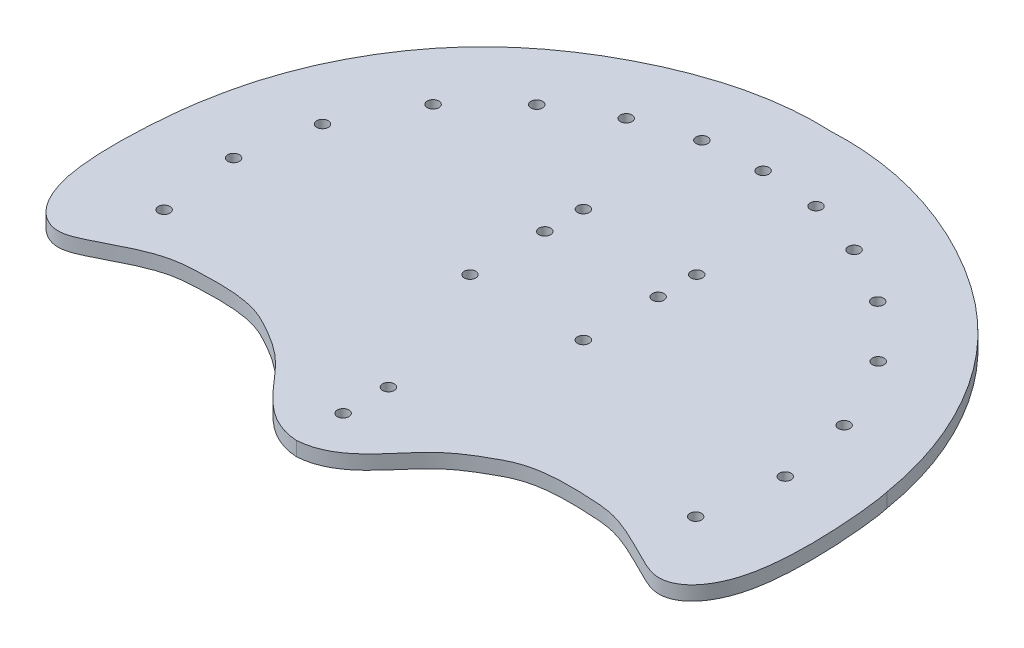
SolidWorks part; units mm, degrees
material "6061-T6 (SS)"
ref_plane "Front Plane" through (0, 0, 0) normal (0, 0, 1) x (1, 0, 0)
ref_plane "Top Plane" through (0, 0, 0) normal (0, 1, 0) x (1, 0, 0)
ref_plane "Right Plane" through (0, 0, 0) normal (1, 0, 0) x (0, 0, -1)
sketch "Sketch3" plane through (0, 0, 0) normal (0, 1, 0) x (1, 0, 0)
  line L0 (0, 0) -> (0, 159.1899) construction
  line L1 (0, 0) -> (0, -140.5301) construction
  line L2 (0, 0) -> (-190.5, 0) construction
  line L3 (0, 0) -> (190.5, 0) construction
  spline S0 degree 3 poles (-190.5, 0) (-184.3927, 37.537) (-157.2613, 93.9641) (-82.3875, 146.6227) (-31.3114, 160.7999) (0, 159.1899) knots 0 0 0 0 0.424401 0.65637 1 1 1 1
  spline S1 degree 3 poles (-190.5, 0) (-192.064, -4.9635) (-201.9672, -83.3146) (-174.6966, -109.29) (-151.6301, -100.568) (-131.4108, -87.7198) (-96.8436, -85.3754) (-78.6925, -86.2588) (-58.8335, -96.8794) (-37.3059, -109.9358) (-21.3496, -139.1148) (0, -140.5301) knots 0 0 0 0 0.166997 0.292321 0.319633 0.426735 0.458914 0.609242 0.64191 0.766802 1 1 1 1
  spline S2 degree 3 poles (190.5, 0) (192.064, -4.9635) (201.9672, -83.3146) (174.6966, -109.29) (151.6301, -100.568) (131.4108, -87.7198) (96.8436, -85.3754) (78.6925, -86.2588) (58.8335, -96.8794) (37.3059, -109.9358) (21.3496, -139.1148) (0, -140.5301) knots 0 0 0 0 0.166997 0.292321 0.319633 0.426735 0.458914 0.609242 0.64191 0.766802 1 1 1 1
  spline S3 degree 3 poles (190.5, 0) (184.3927, 37.537) (157.2613, 93.9641) (82.3875, 146.6227) (31.3114, 160.7999) (0, 159.1899) knots 0 0 0 0 0.424401 0.65637 1 1 1 1
  dimension "D1" = 381
  dimension "D2" = 299.72
  dimension "D3" = 159.1899
  dimension "D4" = 86.8953
  dimension "D5" = 104.4979
  dimension "D6" = 29.1616
  dimension "D7" = 92.2742
  dimension "D8" = 108.411
  dimension "D9" = 67.4883
  dimension "D10" = 43.7314
  dimension "D11" = 117.6915
  dimension "D12" = 162.2568
  dimension "D13" = 89.4522
  dimension "D14" = 140.1036
  dimension "D15" = 175.0666
  dimension "D16" = 50.2669
  dimension "D17" = 101.3666
  dimension "D18" = 138.1225
  dimension "D19" = 155.1557
  dimension "D20" = 192.0074
  dimension "D21" = 193.9268
  dimension "D23" = 76.6666
extrude "Boss-Extrude1" add sketch "Sketch3" along normal blind 7.9502 from surface starting at plane "Top Plane"
sketch "Sketch5" plane through (0, 0, 0) normal (0, -1, 0) x (1, 0, 0)
  line L0 (0, 0) -> (0, -20.32) construction
  line L1 (31.75, -52.07) -> (-31.75, -52.07)
  line L2 (31.75, -52.07) -> (31.75, 11.43)
  line L3 (31.75, 11.43) -> (-31.75, 11.43)
  line L4 (-31.75, -52.07) -> (-31.75, 11.43)
  line L5 (31.75, -52.07) -> (-31.75, 11.43) construction
  line L6 (31.75, 11.43) -> (-31.75, -52.07) construction
  line L7 (-31.75, -52.07) -> (-31.75, -30.48)
  line L8 (-31.75, -30.48) -> (31.75, -30.48) construction
  line L9 (0, -20.32) -> (140.7253, -20.32) construction
  line L10 (0, -20.32) -> (0, -97.1287) construction
  line L11 (0, -20.32) -> (31.9753, -118.7297) construction
  line L13 (0, -20.32) -> (63.8443, -108.1942) construction
  line L14 (0, -20.32) -> (95.5392, -89.7333) construction
  line L15 (124.7166, -60.8429) -> (0, -20.32) construction
  line L16 (0, -20.32) -> (154.5508, 21.0918) construction
  line L17 (0, -20.32) -> (148.922, 65.6601) construction
  line L18 (0, -20.32) -> (-31.9753, -118.7297) construction
  line L19 (0, -20.32) -> (-63.8443, -108.1942) construction
  line L20 (0, -20.32) -> (-95.5392, -89.7333) construction
  line L21 (-124.7166, -60.8429) -> (0, -20.32) construction
  line L22 (0, -20.32) -> (-154.5508, 21.0918) construction
  line L23 (0, -20.32) -> (-148.922, 65.6601) construction
  spline S0 degree 3 poles (-148.922, 65.6601) (-157.8584, 40.2253) (-156.2837, 8.5854) (-143.1202, -28.9506) (-139.3242, -37.3463) (-130.3709, -53.1962) (-125.215, -60.649) (-118.0488, -69.1403) (-116.5795, -70.7975) (-113.5719, -74.0252) (-112.0368, -75.592) (-107.2801, -80.2116) (-103.9215, -83.1695) (-93.3361, -91.6595) (-85.5959, -96.8074) (-76.3408, -101.9556) (-75.3049, -102.5187) (-73.219, -103.6268) (-72.1677, -104.1726) (-69.0049, -105.7765) (-66.8862, -106.8006) (-60.5068, -109.7299) (-56.2231, -111.4921) (-47.6308, -114.6027) (-43.3223, -115.9511) (-34.7104, -118.209) (-30.4072, -119.1185) (-21.8242, -120.4791) (-17.5446, -120.9304) (-11.1443, -121.2499) (-9.0138, -121.2968) (-5.8216, -121.2757) (-4.1848, -121.2414) (-2.5489, -121.1705) (-1.9677, -121.1408) (-1.9605, -121.1404) (-1.2995, -121.1064) (-0.6497, -121.073) (0, -121.0396) knots -0.292878 -0.292878 -0.292878 -0.292878 0.125 0.125 0.25 0.25 0.375 0.375 0.40625 0.40625 0.4375 0.4375 0.5 0.5 0.625 0.625 0.640625 0.640625 0.65625 0.65625 0.6875 0.6875 0.75 0.75 0.8125 0.8125 0.875 0.875 0.9375 0.9375 0.96875 0.96875 0.984375 0.992798 0.992798 0.99292 0.99292 1 1 1 1
  spline S5 degree 3 poles (998.6789, -69.6893) (665.1581, -86.8384) (331.6156, -103.9885) (-1.9268, -121.1387) (-1.9605, -121.1404) (-1.9677, -121.1408) (-2.5489, -121.1705) (-4.1848, -121.2414) (-5.8216, -121.2757) (-9.0138, -121.2968) (-11.1443, -121.2499) (-17.5446, -120.9304) (-21.8242, -120.4791) (-30.4072, -119.1185) (-34.7104, -118.209) (-43.3223, -115.9511) (-47.6308, -114.6027) (-56.2231, -111.4921) (-60.5068, -109.7299) (-66.8862, -106.8006) (-69.0049, -105.7765) (-72.1677, -104.1726) (-73.219, -103.6268) (-75.3049, -102.5187) (-76.3408, -101.9556) (-85.5959, -96.8074) (-93.3361, -91.6595) (-103.9215, -83.1695) (-107.2801, -80.2116) (-112.0368, -75.592) (-113.5719, -74.0252) (-116.5795, -70.7975) (-118.0488, -69.1403) (-125.215, -60.649) (-130.3709, -53.1962) (-139.3242, -37.3463) (-143.1202, -28.9506) (-198.5095, 128.9933) (-22.362, 351.6373) (651.8169, -587.5188) knots -3.627409 -3.627409 -3.627409 -3.627409 0.006836 0.00708 0.00708 0.007202 0.007202 0.015625 0.03125 0.03125 0.0625 0.0625 0.125 0.125 0.1875 0.1875 0.25 0.25 0.3125 0.3125 0.34375 0.34375 0.359375 0.359375 0.375 0.375 0.5 0.5 0.5625 0.5625 0.59375 0.59375 0.625 0.625 0.75 0.75 0.875 0.875 3.034324 3.034324 3.034324 3.034324 only from (0, -121.0396) to (-152.8945, 6.1184)
  spline S6 degree 3 poles (-1687.8289, -2297.0686) (-150.4269, 537.0593) (218.9922, 187.4002) (143.1202, -28.9506) (139.3242, -37.3463) (130.3709, -53.1962) (125.215, -60.649) (118.0488, -69.1403) (116.5795, -70.7975) (113.5719, -74.0252) (112.0368, -75.592) (107.2801, -80.2116) (103.9215, -83.1695) (93.3361, -91.6595) (85.5959, -96.8074) (76.3408, -101.9556) (75.3049, -102.5187) (73.219, -103.6268) (72.1677, -104.1726) (69.0049, -105.7765) (66.8862, -106.8006) (60.5068, -109.7299) (56.2231, -111.4921) (47.6308, -114.6027) (43.3223, -115.9511) (34.7104, -118.209) (30.4072, -119.1185) (21.8242, -120.4791) (17.5446, -120.9304) (11.1443, -121.2499) (9.0138, -121.2968) (5.8216, -121.2757) (4.1848, -121.2414) (2.5489, -121.1705) (1.9677, -121.1408) (1.9605, -121.1404) (-997.3522, -69.7575) (-1996.6535, -18.3753) (-2996.029, 33.0152) knots -2.879056 -2.879056 -2.879056 -2.879056 0.125 0.125 0.25 0.25 0.375 0.375 0.40625 0.40625 0.4375 0.4375 0.5 0.5 0.625 0.625 0.640625 0.640625 0.65625 0.65625 0.6875 0.6875 0.75 0.75 0.8125 0.8125 0.875 0.875 0.9375 0.9375 0.96875 0.96875 0.984375 0.992798 0.992798 0.99292 0.99292 11.881939 11.881939 11.881939 11.881939 only from (152.8945, 6.1184) to (0, -121.0396)
  spline S8 degree 3 poles (148.922, 65.6601) (157.8584, 40.2253) (156.2837, 8.5854) (143.1202, -28.9506) (139.3242, -37.3463) (130.3709, -53.1962) (125.215, -60.649) (118.0488, -69.1403) (116.5795, -70.7975) (113.5719, -74.0252) (112.0368, -75.592) (107.2801, -80.2116) (103.9215, -83.1695) (93.3361, -91.6595) (85.5959, -96.8074) (76.3408, -101.9556) (75.3049, -102.5187) (73.219, -103.6268) (72.1677, -104.1726) (69.0049, -105.7765) (66.8862, -106.8006) (60.5068, -109.7299) (56.2231, -111.4921) (47.6308, -114.6027) (43.3223, -115.9511) (34.7104, -118.209) (30.4072, -119.1185) (21.8242, -120.4791) (17.5446, -120.9304) (11.1443, -121.2499) (9.0138, -121.2968) (5.8216, -121.2757) (4.1848, -121.2414) (2.5489, -121.1705) (1.9677, -121.1408) (1.9605, -121.1404) (1.2995, -121.1064) (0.6497, -121.073) (0, -121.0396) knots -0.292878 -0.292878 -0.292878 -0.292878 0.125 0.125 0.25 0.25 0.375 0.375 0.40625 0.40625 0.4375 0.4375 0.5 0.5 0.625 0.625 0.640625 0.640625 0.65625 0.65625 0.6875 0.6875 0.75 0.75 0.8125 0.8125 0.875 0.875 0.9375 0.9375 0.96875 0.96875 0.984375 0.992798 0.992798 0.99292 0.99292 1 1 1 1
  point P0 (0, -20.32)
  point P3 (0, -20.32)
  point P14 (0, 114.3)
  point P16 (0, 88.9)
  point P26 (148.922, 63.1206)
  dimension "D2" = 63.5
  dimension "D3" = 63.5
  dimension "D4" = 21.59
  dimension "D6" = 25.4
  dimension "D7" = 88.9
  dimension "D8" = 18
  dimension "D9" = 18
  dimension "D10" = 18
  dimension "D11" = 18
  dimension "D12" = 15
  dimension "D13" = 15
  dimension "D5" = 38.1
hole_wizard "F (0.257) Diameter Hole2" positions "Sketch6" profile "Sketch7" hole size "F" standard "ANSI Inch" end condition through all
sketch "Sketch6" plane through (0, 0, 0) normal (0, -1, 0) x (-1, 0, 0)
  line L0 (200000, 20.32) -> (-200140.7253, 20.32) construction
  spline S0 degree 3 poles (-148.922, -65.6601) (-157.8584, -40.2253) (-156.2837, -8.5854) (-143.1202, 28.9506) (-139.3242, 37.3463) (-130.3709, 53.1962) (-125.215, 60.649) (-118.0488, 69.1403) (-116.5795, 70.7975) (-113.5719, 74.0252) (-112.0368, 75.592) (-107.2801, 80.2116) (-103.9215, 83.1695) (-93.3361, 91.6595) (-85.5959, 96.8074) (-76.3408, 101.9556) (-75.3049, 102.5187) (-73.219, 103.6268) (-72.1677, 104.1726) (-69.0049, 105.7765) (-66.8862, 106.8006) (-60.5068, 109.7299) (-56.2231, 111.4921) (-47.6308, 114.6027) (-43.3223, 115.9511) (-34.7104, 118.209) (-30.4072, 119.1185) (-21.8242, 120.4791) (-17.5446, 120.9304) (-11.1443, 121.2499) (-9.0138, 121.2968) (-5.8216, 121.2757) (-4.1848, 121.2414) (-2.5489, 121.1705) (-1.9677, 121.1408) (-1.9605, 121.1404) (-1.2995, 121.1064) (-0.6497, 121.073) (0, 121.0396) knots -0.292878 -0.292878 -0.292878 -0.292878 0.125 0.125 0.25 0.25 0.375 0.375 0.40625 0.40625 0.4375 0.4375 0.5 0.5 0.625 0.625 0.640625 0.640625 0.65625 0.65625 0.6875 0.6875 0.75 0.75 0.8125 0.8125 0.875 0.875 0.9375 0.9375 0.96875 0.96875 0.984375 0.992798 0.992798 0.99292 0.99292 1 1 1 1 construction
  spline S1 degree 3 poles (148.922, -65.6601) (157.8584, -40.2253) (156.2837, -8.5854) (143.1202, 28.9506) (139.3242, 37.3463) (130.3709, 53.1962) (125.215, 60.649) (118.0488, 69.1403) (116.5795, 70.7975) (113.5719, 74.0252) (112.0368, 75.592) (107.2801, 80.2116) (103.9215, 83.1695) (93.3361, 91.6595) (85.5959, 96.8074) (76.3408, 101.9556) (75.3049, 102.5187) (73.219, 103.6268) (72.1677, 104.1726) (69.0049, 105.7765) (66.8862, 106.8006) (60.5068, 109.7299) (56.2231, 111.4921) (47.6308, 114.6027) (43.3223, 115.9511) (34.7104, 118.209) (30.4072, 119.1185) (21.8242, 120.4791) (17.5446, 120.9304) (11.1443, 121.2499) (9.0138, 121.2968) (5.8216, 121.2757) (4.1848, 121.2414) (2.5489, 121.1705) (1.9677, 121.1408) (1.9605, 121.1404) (1.2995, 121.1064) (0.6497, 121.073) (0, 121.0396) knots -0.292878 -0.292878 -0.292878 -0.292878 0.125 0.125 0.25 0.25 0.375 0.375 0.40625 0.40625 0.4375 0.4375 0.5 0.5 0.625 0.625 0.640625 0.640625 0.65625 0.65625 0.6875 0.6875 0.75 0.75 0.8125 0.8125 0.875 0.875 0.9375 0.9375 0.96875 0.96875 0.984375 0.992798 0.992798 0.99292 0.99292 1 1 1 1 construction
  point P3 (31.75, 52.07)
  point P6 (31.75, -11.43)
  point P9 (-31.75, -11.43)
  point P15 (31.75, 30.48)
  point P32 (-31.75, 30.48)
  point P39 (-31.75, 52.07)
  point P42 (-154.5508, -21.0918)
  point P45 (-148.922, -65.6601)
  point P48 (-146.1469, 20.32)
  point P54 (-124.7166, 60.8429)
  point P57 (-95.5392, 89.7333)
  point P60 (148.922, -65.6601)
  point P63 (154.5508, -21.0918)
  point P66 (124.7166, 60.8429)
  point P69 (95.5392, 89.7333)
  point P72 (63.8443, 108.1942)
  point P76 (31.9753, 118.7297)
  point P79 (0, 121.0396)
  point P82 (-31.9753, 118.7297)
  point P85 (-63.8443, 108.1942)
  point P88 (-95.5392, 89.7333)
  point P91 (146.1469, 20.32)
  point P95 (0, -88.9)
  point P98 (0, -114.3)
  point P102 (63.8443, 108.1942)
sketch "Sketch7" plane through (-31.75, 0, -52.07) normal (1, 0, 0) x (0, 0, -1)
  line L0 (0, 0) -> (0, 7.9502)
  line L1 (0, 7.9502) -> (3.2639, 7.9502)
  line L2 (3.2639, 7.9502) -> (3.2639, 0)
  line L5 (3.2639, 0) -> (0, 0)
  line L11 (0, -6.35) -> (0, 107.95) construction
  dimension "Thru Hole Dia." = 6.5278
  dimension "Thru Hole Depth" = 7.9502
sketch "Sketch9" plane through (0, 7.9502, 0) normal (0, 1, 0) x (1, 0, 0)
  line L0 (102.3823, -86.0787) -> (102.3823, 130.9193)
  line L1 (-50.7649, -102.4301) -> (50.7649, -102.4301)
  spline S0 degree 3 poles (0, -140.5301) (21.3496, -139.1148) (37.3059, -109.9358) (58.8335, -96.8794) (78.6925, -86.2588) (96.8436, -85.3754) (131.4108, -87.7198) (151.6301, -100.568) (174.6966, -109.29) (201.9672, -83.3146) (192.064, -4.9635) (190.5, 0) knots 0 0 0 0 0.233198 0.35809 0.390758 0.541086 0.573265 0.680367 0.707679 0.833003 1 1 1 1 construction
  spline S1 degree 3 poles (190.5, 0) (184.3927, 37.537) (157.2613, 93.9641) (82.3875, 146.6227) (31.3114, 160.7999) (0, 159.1899) knots 0 0 0 0 0.424401 0.65637 1 1 1 1 construction
  spline S2 degree 3 poles (-190.5, 0) (-192.064, -4.9635) (-201.9672, -83.3146) (-174.6966, -109.29) (-151.6301, -100.568) (-131.4108, -87.7198) (-96.8436, -85.3754) (-78.6925, -86.2588) (-58.8335, -96.8794) (-37.3059, -109.9358) (-21.3496, -139.1148) (0, -140.5301) knots 0 0 0 0 0.166997 0.292321 0.319633 0.426735 0.458914 0.609242 0.64191 0.766802 1 1 1 1 construction
  dimension "D1" = 38.1
split line "Split Line1" [suppressed]
equation "\"Plate thickness\"=0.313"
equation "\"D1@Boss-Extrude1\"=\"Plate thickness\""
equation "\"Bracket Alignment\"= .80"
equation "\"D1@Sketch5\"=\"Bracket Alignment\""
